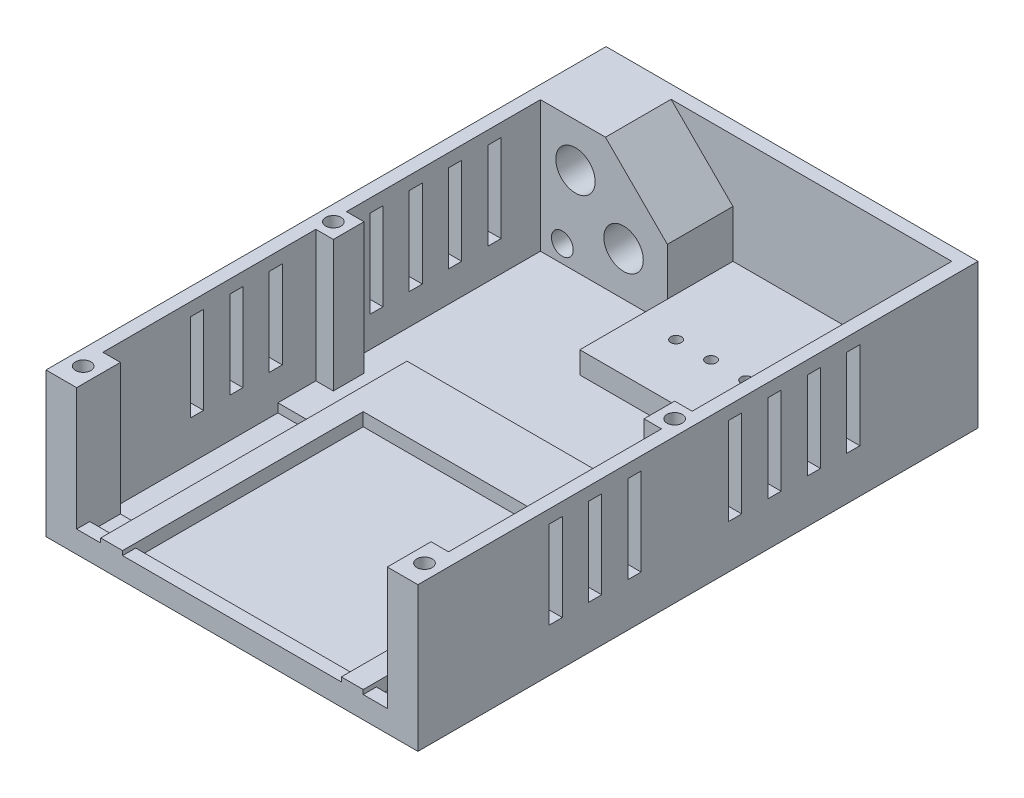
SolidWorks part; units mm, degrees
ref_plane "Front Plane" through (0, 0, 0) normal (0, 0, 1) x (1, 0, 0)
ref_plane "Top Plane" through (0, 0, 0) normal (0, 1, 0) x (1, 0, 0)
ref_plane "Right Plane" through (0, 0, 0) normal (1, 0, 0) x (0, 0, -1)
sketch "Sketch2" plane through (0, 0, 0) normal (0, 1, 0) x (1, 0, 0)
  line L1 (39.5, -62.5) -> (-39.5, -62.5)
  line L2 (39.5, -62.5) -> (39.5, 62.5)
  line L3 (39.5, 62.5) -> (-39.5, 62.5)
  line L4 (-39.5, -62.5) -> (-39.5, 62.5)
  line L5 (39.5, -62.5) -> (-39.5, 62.5) construction
  line L6 (39.5, 62.5) -> (-39.5, -62.5) construction
  point P0 (0, 0)
  dimension "D1" = 79
  dimension "D2" = 125
extrude "Boss-Extrude1" add sketch "Sketch2" along normal blind 3
sketch "Sketch9" plane through (0, 0, 0) normal (0, 1, 0) x (1, 0, 0)
  line L2 (-39.5, 62.5) -> (-39.5, -62.5)
  line L3 (-39.5, -62.5) -> (-42.5, -62.5)
  line L4 (-42.5, 65.5) -> (-42.5, -62.5)
  line L6 (39.5, 62.5) -> (39.5, -62.5)
  line L7 (39.5, -62.5) -> (42.5, -62.5)
  line L8 (42.5, 65.5) -> (42.5, -62.5)
  line L9 (39.5, 62.5) -> (-39.5, 62.5)
  line L11 (42.5, 65.5) -> (-42.5, 65.5)
  dimension "D1" = 3
  dimension "D2" = 3
  dimension "D3" = 3
sketch "Sketch3" plane through (0, 3, 0) normal (0, 1, 0) x (1, 0, 0)
  line L0 (0, -62.5) -> (0, 62.5) construction
  line L1 (-39.5, -62.5) -> (39.5, -62.5) construction
  line L2 (39.5, 62.5) -> (-39.5, 62.5) construction
  line L4 (30, -62.5) -> (-30, -62.5)
  line L5 (30, -62.5) -> (30, 7.5)
  line L6 (30, 7.5) -> (-30, 7.5)
  line L7 (-30, -62.5) -> (-30, 7.5)
  line L8 (30, -62.5) -> (-30, 7.5) construction
  line L9 (30, 7.5) -> (-30, -62.5) construction
  point P6 (0, -27.5)
  dimension "D1" = 60
  dimension "D2" = 70
extrude "support" add sketch "Sketch3" along normal blind 3
sketch "Sketch4" plane through (0, 6, 0) normal (0, 1, 0) x (1, 0, 0)
  line L0 (-30, -62.5) -> (30, -62.5) construction
  line L1 (-25, -62.5) -> (25, -62.5)
  line L2 (-25, -62.5) -> (-25, -7.5)
  line L3 (-25, -7.5) -> (25, -7.5)
  line L4 (25, -62.5) -> (25, -7.5)
  line L5 (30, 7.5) -> (-30, 7.5) construction
  line L6 (30, -62.5) -> (30, 7.5) construction
  line L7 (-30, 7.5) -> (-30, -62.5) construction
  dimension "D1" = 15
  dimension "D2" = 5
  dimension "D3" = 5
extrude "remove plastic" cut sketch "Sketch4" against normal blind 3
sketch "Sketch5" plane through (0, 3, 0) normal (0, 1, 0) x (1, 0, 0)
  line L1 (-10.5, 62.5) -> (39.5, 62.5)
  line L2 (-10.5, 62.5) -> (-10.5, 27.5)
  line L3 (-10.5, 27.5) -> (39.5, 27.5)
  line L4 (39.5, 62.5) -> (39.5, 27.5)
  line L5 (39.5, -62.5) -> (39.5, 62.5) construction
  line L7 (30, -62.5) -> (39.5, -62.5) construction
  line L8 (39.5, 62.5) -> (-39.5, 62.5) construction
  dimension "D1" = 50
  dimension "D3" = 90
extrude "Boss-Extrude3" add sketch "Sketch5" along normal blind 5
sketch "Sketch6" plane through (0, 8, 0) normal (0, 1, 0) x (1, 0, 0)
  line L0 (-10.5, 40.5) -> (39.5, 40.5) construction
  line L3 (14.5, 62.5) -> (14.5, 27.5) construction
  line L4 (39.5, 62.5) -> (-10.5, 62.5) construction
  line L5 (-10.5, 27.5) -> (39.5, 27.5) construction
  line L8 (-10.5, 27.5) -> (39.5, 27.5) construction
  circle A0 centre (-1.5, 40.5) radius 1.2
  circle A1 centre (6.5, 40.5) radius 1.2
  circle A2 centre (14.5, 40.5) radius 1.2
  circle A3 centre (22.5, 40.5) radius 1.2
  circle A4 centre (30.5, 40.5) radius 1.2
  dimension "D1" = 2.4
  dimension "D2" = 8
  dimension "D3" = 8
  dimension "D4" = 8
  dimension "D5" = 8
  dimension "D6" = 13
extrude "Cut-Extrude2" cut sketch "Sketch6" against normal blind 5 draft 1
sketch "Sketch7" plane through (0, 3, 0) normal (0, 1, 0) x (1, 0, 0)
  line L0 (-39.5, 62.5) -> (-39.5, -62.5) construction
  line L1 (-10.5, 62.5) -> (-39.5, 62.5)
  line L2 (-10.5, 62.5) -> (-10.5, 47.5)
  line L3 (-10.5, 47.5) -> (-39.5, 47.5)
  line L4 (-39.5, 62.5) -> (-39.5, 47.5)
  dimension "D1" = 15
extrude "cable block" add sketch "Sketch7" along normal blind 30
extrude "walls" add sketch "Sketch9" along normal up to surface (33 mm away) up to face at (-25, 33, -55)
sketch "Sketch8" plane through (0, 0, -47.5) normal (0, 0, 1) x (1, 0, 0)
  line L0 (-10.5, 33) -> (-10.5, 8) construction
  line L2 (-39.5, 33) -> (-10.5, 33) construction
  line L4 (-39.5, 3) -> (-10.5, 3) construction
  line L5 (-39.5, 33) -> (-39.5, 3) construction
  circle A0 centre (-20.5, 13) radius 4.5
  circle A1 centre (-34.5, 7) radius 2.5
  circle A2 centre (-31.5, 23) radius 4.5
  dimension "D1" = 9
  dimension "D2" = 5
  dimension "D3" = 10
  dimension "D8" = 10
  dimension "D4" = 8
  dimension "D5" = 10
  dimension "D6" = 5
  dimension "D7" = 4
extrude "cable holes round" cut sketch "Sketch8" against normal blind 31
sketch "Sketch10" plane through (0, 3, 0) normal (0, 1, 0) x (1, 0, 0)
  line L0 (0, -62.5) -> (0, -7.5) construction
  line L1 (-25, -62.5) -> (25, -62.5) construction
  line L2 (25, -7.5) -> (-25, -7.5) construction
  line L3 (-35.5, -62.5) -> (35.5, -62.5) construction
  line L4 (39.5, -62.5) -> (39.5, 27.5) construction
  line L5 (-39.5, -62.5) -> (-35.5, -62.5)
  line L6 (-39.5, -62.5) -> (-39.5, -52.5)
  line L7 (-39.5, -52.5) -> (-35.5, -52.5)
  line L8 (-35.5, -62.5) -> (-35.5, -52.5)
  line L9 (35.5, -62.5) -> (39.5, -62.5)
  line L10 (35.5, -62.5) -> (35.5, -52.5)
  line L11 (35.5, -52.5) -> (39.5, -52.5)
  line L12 (39.5, -62.5) -> (39.5, -52.5)
  dimension "D1" = 71
  dimension "D2" = 10
  dimension "D3" = 10
extrude "Lid screw posts front" add sketch "Sketch10" along normal up to surface (30 mm away) up to face at (-2.1, 33, -10.1)
sketch "Sketch11" plane through (0, 0, -62.5) normal (0, 0, 1) x (1, 0, 0)
  line L0 (14.5, 18) -> (32.5, 18)
  line L1 (39.5, 33) -> (39.5, 8) construction
  line L2 (14.5, 8) -> (32.5, 8)
  line L5 (39.5, 8) -> (-10.5, 8) construction
  arc A0 (14.5, 18) -> (14.5, 8) centre (14.5, 13) ccw
  arc A1 (32.5, 8) -> (32.5, 18) centre (32.5, 13) ccw
  dimension "D1" = 7
  dimension "D2" = 10
  dimension "D3" = 10
  dimension "D4" = 18
extrude "Cable cutout" [suppressed] cut sketch "Sketch11" against normal up to surface (3 mm away) up to face at (-27, 23, -65.5)
sketch "Sketch12" plane through (0, 0, -47.5) normal (0, 0, 1) x (1, 0, 0)
  line L0 (-24.6421, 33) -> (-10.5, 18.8579)
  line L1 (-39.5, 33) -> (-10.5, 33) construction
  line L2 (-10.5, 33) -> (-10.5, 8) construction
  line L3 (-10.5, 18.8579) -> (-10.5, 33)
  line L4 (-10.5, 33) -> (-24.6421, 33)
  dimension "D1" = 45
  dimension "D2" = 20
extrude "remove Material" cut sketch "Sketch12" against normal up to surface (15 mm away) up to face at (14.5, 20.5, -62.5)
sketch "Sketch13" plane through (0, 3, 0) normal (0, 1, 0) x (1, 0, 0)
  line L0 (-39.5, 47.5) -> (-39.5, -52.5) construction
  line L1 (-39.5, -3.8301) -> (-35.5, -3.8301)
  line L2 (-39.5, -3.8301) -> (-39.5, 3.1699)
  line L3 (-39.5, 3.1699) -> (-35.5, 3.1699)
  line L4 (-35.5, -3.8301) -> (-35.5, 3.1699)
  line L5 (39.5, -52.5) -> (39.5, 27.5) construction
  line L6 (39.5, 3.1699) -> (35.5, 3.1699)
  line L7 (39.5, 3.1699) -> (39.5, -3.8301)
  line L8 (39.5, -3.8301) -> (35.5, -3.8301)
  line L9 (35.5, 3.1699) -> (35.5, -3.8301)
  dimension "D1" = 4
  dimension "D2" = 7
  dimension "D3" = 7
  dimension "D4" = 7
  dimension "D5" = 4
  dimension "D6" = 7
extrude "Lid screw posts back" add sketch "Sketch13" along normal up to surface (30 mm away) up to face at (-3.5203, 33, 7.7857)
sketch "Sketch14" plane through (0, 33, 0) normal (0, 1, 0) x (1, 0, 0)
  line L0 (-35.5, -62.5) -> (-42.5, -62.5) construction
  line L2 (42.5, -62.5) -> (35.5, -62.5) construction
  line L3 (42.5, 65.5) -> (42.5, -62.5) construction
  line L4 (39.5, -3.8301) -> (35.5, -3.8301) construction
  line L5 (-35.5, -3.8301) -> (-39.5, -3.8301) construction
  line L6 (-42.5, -62.5) -> (-42.5, 65.5) construction
  circle A0 centre (-39, -57.5) radius 1.75
  circle A1 centre (39, -57.5) radius 1.75
  circle A2 centre (39, -0.3301) radius 1.75
  circle A3 centre (-39, -0.3301) radius 1.75
  dimension "D1" = 3.5
  dimension "D2" = 5
  dimension "D3" = 3.5
  dimension "D4" = 5
  dimension "D5" = 3.5
  dimension "D6" = 3.5
  dimension "D7" = 3.5
  dimension "D8" = 3.5
  dimension "D9" = 3.5
extrude "Lid screw holes" cut sketch "Sketch14" against normal blind 20 draft 1
sketch "Sketch16" plane through (0, 3, 0) normal (0, 1, 0) x (1, 0, 0)
  line L0 (-30, 7.5) -> (-30, -62.5) construction
  line L1 (-39.5, -52.5) -> (-30, -52.5)
  line L2 (-39.5, -52.5) -> (-39.5, -12.5)
  line L3 (-39.5, -12.5) -> (-30, -12.5)
  line L4 (-30, -52.5) -> (-30, -12.5)
  line L5 (30, -62.5) -> (30, 7.5) construction
  line L6 (39.5, -52.5) -> (30, -52.5)
  line L7 (39.5, -52.5) -> (39.5, -12.5)
  line L8 (39.5, -12.5) -> (30, -12.5)
  line L9 (30, -52.5) -> (30, -12.5)
  dimension "D1" = 20
  dimension "D2" = 20
extrude "Sliders" cut sketch "Sketch16" against normal blind 2
sketch "Sketch17" plane through (0, 0, 62.5) normal (0, 0, 1) x (1, 0, 0)
  line L0 (35.5, 33) -> (35.5, 3) construction
  line L1 (-35.5, 3) -> (35.5, 3)
  line L2 (-35.5, 3) -> (-35.5, 5)
  line L3 (-35.5, 5) -> (35.5, 5)
  line L4 (35.5, 3) -> (35.5, 5)
  dimension "D1" = 2
extrude "Front Lip" add sketch "Sketch17" against normal blind 3
sketch "Sketch19" plane through (42.5, 0, 0) normal (1, 0, 0) x (0, 0, -1)
  line L0 (65.5, 20) -> (11.5, 20) construction
  line L1 (65.5, 33) -> (65.5, 0) construction
  line L2 (38.5, 20) -> (35.5, 20) construction
  line L7 (65.5, 33) -> (-62.5, 33) construction
  line L16 (32.5, 33) -> (32.5, 27.4267) construction
  line L17 (23.5, 33) -> (23.5, 27.4664) construction
  line L18 (38.5, 10) -> (35.5, 10)
  line L19 (35.5, 30) -> (35.5, 10)
  line L20 (38.5, 30) -> (38.5, 10)
  line L21 (38.5, 30) -> (35.5, 30)
  line L22 (26.5, 30) -> (26.5, 10)
  line L23 (26.5, 10) -> (29.5, 10)
  line L24 (29.5, 30) -> (29.5, 10)
  line L25 (26.5, 30) -> (29.5, 30)
  line L26 (20.5, 30) -> (17.5, 30)
  line L27 (20.5, 10) -> (17.5, 10)
  line L28 (17.5, 30) -> (17.5, 10)
  line L29 (20.5, 30) -> (20.5, 10)
  line L30 (14.5, 33) -> (14.5, 27.5061) construction
  line L31 (8.5, 10) -> (11.5, 10)
  line L32 (8.5, 30) -> (8.5, 10)
  line L33 (11.5, 30) -> (11.5, 10)
  line L34 (8.5, 30) -> (11.5, 30)
  line L35 (-1.5, 33) -> (-1.5, 27.5767) construction
  line L36 (-11.5, 10) -> (-14.5, 10)
  line L37 (-14.5, 30) -> (-14.5, 10)
  line L38 (-11.5, 30) -> (-11.5, 10)
  line L39 (-11.5, 30) -> (-14.5, 30)
  line L40 (-17.5, 33) -> (-17.5, 27.6473) construction
  line L41 (-23.5, 10) -> (-20.5, 10)
  line L42 (-20.5, 30) -> (-20.5, 10)
  line L43 (-23.5, 30) -> (-23.5, 10)
  line L44 (-23.5, 30) -> (-20.5, 30)
  line L45 (-26.5, 33) -> (-26.5, 25.5009) construction
  line L46 (-29.5, 10) -> (-32.5, 10)
  line L47 (-32.5, 30) -> (-32.5, 10)
  line L48 (-29.5, 30) -> (-29.5, 10)
  line L49 (-29.5, 30) -> (-32.5, 30)
  point P8 (0, 0)
  dimension "D2" = 27
  dimension "D3" = 13
  dimension "D4" = 20
  dimension "D5" = 3
  dimension "D7" = 3
  dimension "D8" = 3
  dimension "D9" = 3
  dimension "D10" = 10
  dimension "D11" = 3
  dimension "D12" = 3
extrude "Cut-Extrude3" cut sketch "Sketch19" against normal up to surface (85 mm away) up to face at (-42.5, 16.5, -1.5)
equation "\"c_outside_width\"= 75mm"
equation "\"c_total_length\"= 80mm"
equation "\"c_inside_width\"= 70mm"
equation "\"wall_thickness\"= 3mm"
equation "\"D1@Sketch2\"=\"c_outside_width\" + \"wall_thickness\" + 1"
equation "\"D1@Boss-Extrude1\"=\"wall_thickness\""
equation "\"c_bottom_support_width\"=60"
equation "\"D1@Sketch3\"=\"c_bottom_support_width\""
equation "\"c_bottom_support_length\"=70"
equation "\"D2@Sketch3\"=\"c_bottom_support_length\""
equation "\"c_bottom_support_height\"= 3mm"
equation "\"D1@support\"=\"c_bottom_support_height\""
equation "\"D1@remove plastic\"=\"c_bottom_support_height\""
equation "\"D1@Sketch9\"=\"wall_thickness\""
equation "\"D2@Sketch9\"=\"wall_thickness\""
equation "\"D3@Sketch9\"=\"wall_thickness\""
equation "\"c__outside_height\"= 34.5mm"
equation "\"c_inside_height\"= 30mm"
equation "\"D1@walls\"=\"c__outside_height\""
equation "\"D1@Sketch10\"=\"c_inside_width\"+1"
equation "\"case_screw_diameter\"=3.5"
equation "\"D1@Sketch14\"=\"case_screw_diameter\""
equation "\"D1@cable block\" = \"c_inside_height\""
